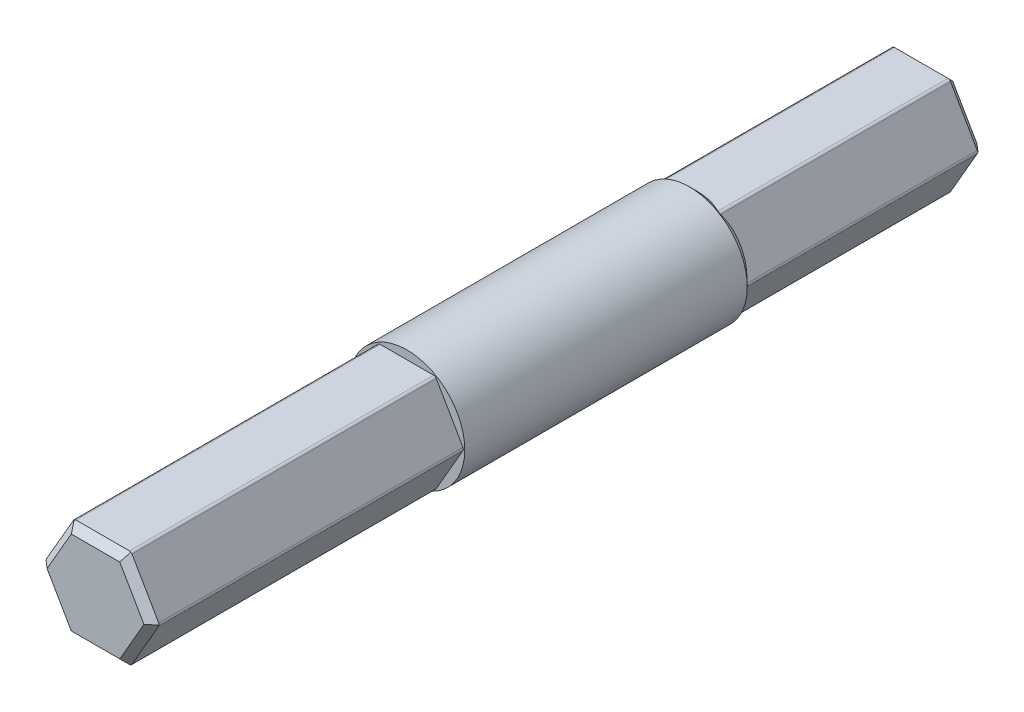
SolidWorks part; units mm, degrees
material "PETG"
ref_plane "Front Plane" through (0, 0, 0) normal (0, 0, 1) x (1, 0, 0)
ref_plane "Top Plane" through (0, 0, 0) normal (0, 1, 0) x (1, 0, 0)
ref_plane "Right Plane" through (0, 0, 0) normal (1, 0, 0) x (0, 0, -1)
sketch "Sketch1" plane through (0, 0, 0) normal (0, 0, 1) x (1, 0, 0)
  circle A0 centre (0, 0) radius 3.99
  dimension "Shaft Dia" = 7.98
extrude "Boss-Extrude1" add sketch "Sketch1" along normal blind 20
sketch "Sketch2" plane through (0, 0, 20) normal (0, 0, 1) x (1, 0, 0)
  line L1 (4, 0) -> (2, 3.4641) construction
  line L2 (2, 3.4641) -> (-2, 3.4641) construction
  line L3 (-2, 3.4641) -> (-4, 0) construction
  line L4 (-4, 0) -> (-2, -3.4641) construction
  line L5 (-2, -3.4641) -> (2, -3.4641) construction
  line L6 (2, -3.4641) -> (4, 0) construction
  line L7 (3.9221, 0) -> (1.961, 3.3966)
  line L8 (1.961, 3.3966) -> (-1.961, 3.3966)
  line L9 (-1.961, 3.3966) -> (-3.9221, 0)
  line L10 (-3.9221, 0) -> (-1.961, -3.3966)
  line L11 (-1.961, -3.3966) -> (1.961, -3.3966)
  line L12 (1.961, -3.3966) -> (3.9221, 0)
  circle A0 centre (0, 0) radius 3.4641 construction
  circle A1 centre (0, 0) radius 3.3966 construction
  dimension "Hex Circumscribed Nominal Dia" = 8
  dimension "Hex Flat To Flat Offset" = 0.0675
extrude "Boss-Extrude2" add sketch "Sketch2" along normal blind 21.5
sketch "Sketch3" plane through (0, 0, 0) normal (0, 0, -1) x (-1, 0, 0)
  line L0 (-1.961, 3.3966) -> (1.961, 3.3966) construction
  line L13 (3.9221, 0) -> (1.961, 3.3966)
  line L14 (1.961, 3.3966) -> (-1.961, 3.3966)
  line L15 (-1.961, 3.3966) -> (-3.9221, 0)
  line L16 (-3.9221, 0) -> (-1.961, -3.3966)
  line L17 (-1.961, -3.3966) -> (1.961, -3.3966)
  line L18 (1.961, -3.3966) -> (3.9221, 0)
  circle A1 centre (0, 0) radius 3.3966 construction
extrude "Boss-Extrude3" add sketch "Sketch3" along normal blind 16
chamfer "Chamfer1" distance 0.5 angle 45 12 edges at (0, -3.3966, 41.5) (-2.9415, -1.6983, 41.5) (-2.9415, 1.6983, 41.5) (0, 3.3966, 41.5) (2.9415, 1.6983, 41.5) (2.9415, -1.6983, 41.5) (0, -3.3966, -16) (2.9415, -1.6983, -16) (2.9415, 1.6983, -16) (0, 3.3966, -16) (-2.9415, 1.6983, -16) (-2.9415, -1.6983, -16)
fillet "Fillet1" radius 0.2 12 edges at (-1.961, 3.3966, -7.75) (-3.9221, 0, -7.75) (1.961, 3.3966, -7.75) (3.9221, 0, -7.75) (1.961, -3.3966, -7.75) (-1.961, -3.3966, -7.75) (1.961, -3.3966, 30.5) (-1.961, -3.3966, 30.5) (-3.9221, 0, 30.5) (-1.961, 3.3966, 30.5) (3.9221, 0, 30.5) (1.961, 3.3966, 30.5)
chamfer "Chamfer2" distance 0.5 angle 45 1 edges at (3.99, 0, 0)
equation "\"tol_dia_id_intfc\" = 0.0200mm ' For hole diameters - Interference fit"
equation "\"tol_dia_id_slip\"  = 0.0300mm ' For hole diameters - Slip fit"
equation "\"tol_dia_id_clear\" = 0.0500mm ' For hole diameters - Clearance fit"
equation "\"tol_dia_od_intfc\" = 0.0200mm ' For shaft diameters - Interference fit"
equation "\"tol_dia_od_slip\"  = 0.0300mm ' For shaft diameters - Slip fit"
equation "\"tol_dia_od_clear\" = 0.0500mm ' For shaft diameters - Clearance fit"
equation "\"tol_general_intfc\"= 0.0030mm ' For general parts (Horiz) - Interference fit"
equation "\"tol_general_slip\" = 0.0050mm ' For general parts (Horiz) - Slip fit"
equation "\"tol_general_clear\"= 0.0100mm ' For general parts (Horiz) - Clearance fit"
equation "\"tol_layer_intfc\"  = 0.0030mm ' For all parts (Vert) - Interference fit"
equation "\"tol_layer_slip\"   = 0.0050mm ' For all parts (Vert) - Slip fit"
equation "\"tol_layer_clear\"  = 0.0100mm ' For all parts (Vert) - Clearance fit"
equation "\"tol_corner_rad\"   = 0.100mm ' For corners that fit into other parts"
equation "\"Shaft Dia@Sketch1\" = \"nominal_dia\" - \"tol_dia_od_intfc\""
equation "\"nominal_dia\"= 8.00mm"
equation "\"Hex Circumscribed Nominal Dia@Sketch2\" = \"nominal_dia\""
equation "\"Hex Flat To Flat Offset@Sketch2\"= \"tol_general_slip\" + 0.0625"
equation "\"D1@Fillet1\"=\"tol_corner_rad\"*2"
equation "\"D1@Boss-Extrude2\"=21.5"
